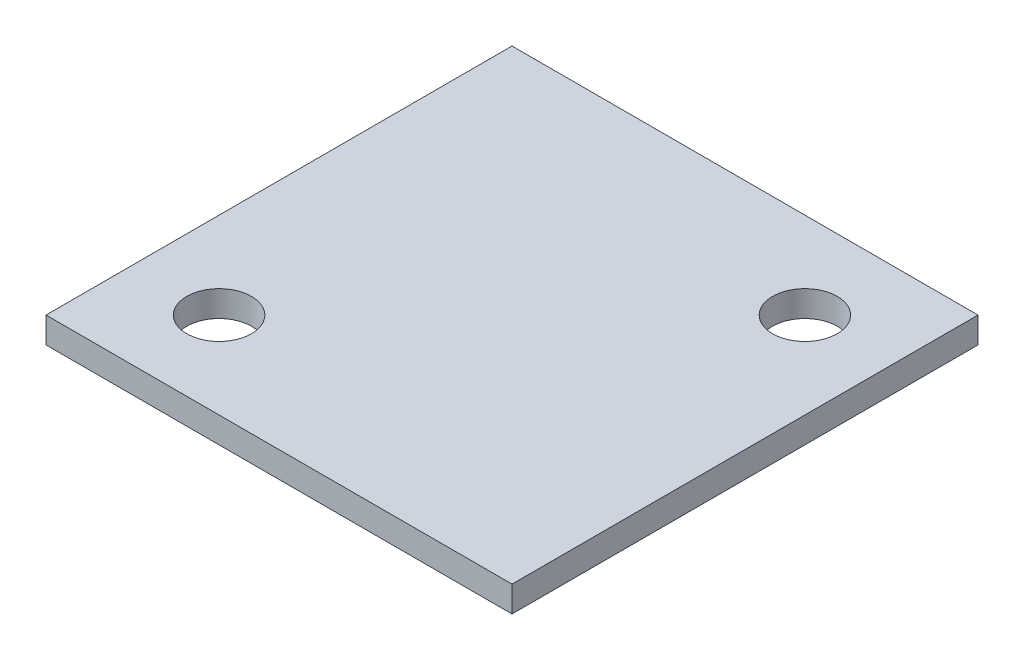
SolidWorks part; units mm, degrees
ref_plane "Front Plane" through (0, 0, 0) normal (0, 0, 1) x (1, 0, 0)
ref_plane "Top Plane" through (0, 0, 0) normal (0, 1, 0) x (1, 0, 0)
ref_plane "Right Plane" through (0, 0, 0) normal (1, 0, 0) x (0, 0, -1)
sketch "Sketch1" plane through (0, 0, 0) normal (0, 1, 0) x (1, 0, 0)
  line L1 (-90, -90) -> (90, -90)
  line L2 (-90, -90) -> (-90, 90)
  line L3 (-90, 90) -> (90, 90)
  line L4 (90, -90) -> (90, 90)
  line L5 (-90, -90) -> (90, 90) construction
  line L6 (-90, 90) -> (90, -90) construction
  point P0 (0, 0)
  dimension "D1" = 180
extrude "Boss-Extrude1" add sketch "Sketch1" along normal blind 10
sketch "Sketch2" plane through (0, 0, 0) normal (0, -1, 0) x (-1, 0, 0)
  line L3 (-56.5685, 56.5685) -> (-90, 90) construction
  line L5 (56.5685, -56.5685) -> (90, -90) construction
  circle A1 centre (-56.5685, 56.5685) radius 12.5
  circle A2 centre (56.5685, -56.5685) radius 12.5
  dimension "D1" = 160
  dimension "D2" = 25
extrude "Cut-Extrude1" cut sketch "Sketch2" against normal up to surface (10 mm away) up to face at (0, 10, 0)
